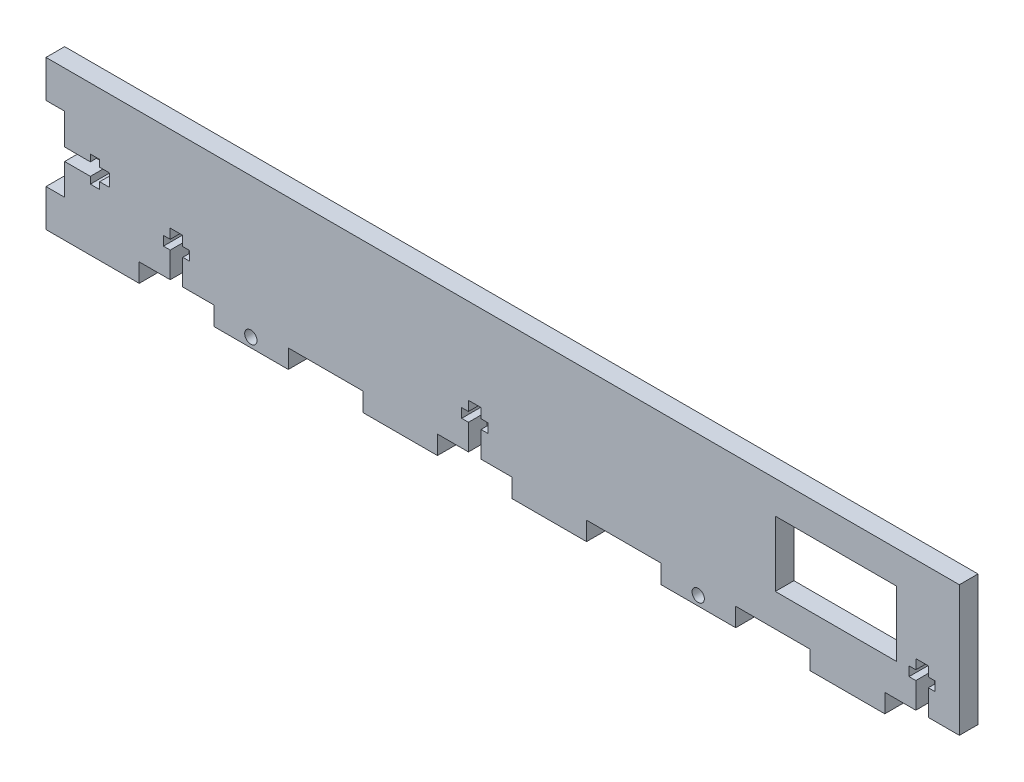
SolidWorks part; units mm, degrees
ref_plane "Front Plane" through (0, 0, 0) normal (0, 0, 1) x (1, 0, 0)
ref_plane "Top Plane" through (0, 0, 0) normal (0, 1, 0) x (1, 0, 0)
ref_plane "Right Plane" through (0, 0, 0) normal (1, 0, 0) x (0, 0, -1)
sketch "Sketch1" plane through (0, 0, 0) normal (0, 0, 1) x (1, 0, 0)
  line L0 (-262.733, -54.9538) -> (-262.733, 69.85) construction
  line L1 (42.067, 22.225) -> (-262.733, 22.225)
  line L2 (42.067, 22.225) -> (42.067, -22.225)
  line L3 (42.067, -22.225) -> (-262.733, -22.225)
  line L4 (-262.733, 22.225) -> (-262.733, -22.225)
  line L5 (63.0291, 0) -> (-62.7737, 0) construction
  line L6 (-19.6295, 10.033) -> (19.6295, 10.033) construction
  line L7 (19.6295, -10.033) -> (-19.6295, -10.033) construction
  line L8 (27.25, 6.27) -> (27.25, 8.0899) construction
  dimension "D1" = 44.45
  dimension "D2" = 14.817
extrude "Boss-Extrude1" add sketch "Sketch1" along normal blind 6.35
sketch "Sketch2" plane through (0, 0, 6.35) normal (0, 0, 1) x (1, 0, 0)
  line L0 (-41.9443, 0) -> (30.2812, 0) construction
  line L1 (-20.6375, 11.1125) -> (20.6375, 11.1125)
  line L2 (-20.6375, 11.1125) -> (-20.6375, -11.1125)
  line L3 (-20.6375, -11.1125) -> (20.6375, -11.1125)
  line L4 (20.6375, 11.1125) -> (20.6375, -11.1125)
  line L5 (-19.6295, 10.033) -> (19.6295, 10.033) construction
  line L6 (19.6295, -10.033) -> (-19.6295, -10.033) construction
  line L7 (0, 34.6052) -> (0, -28.4279) construction
  line L8 (-20.1295, -9.533) -> (-20.1295, 9.533) construction
  line L9 (20.1295, 9.533) -> (20.1295, -9.533) construction
  dimension "D1" = 22.225
  dimension "D2" = 41.275
extrude "Cut-Extrude1" cut sketch "Sketch2" against normal through all
ref_plane "Plane1" through (42.067, -22.225, 6.35) normal (1, 0, 0) x (0, 0, -1)
sketch "Sketch5" plane through (0, -22.225, 0) normal (0, -1, 0) x (1, 0, 0)
  line L0 (-262.733, 6.35) -> (42.067, 6.35) construction
  line L1 (16.667, 6.35) -> (-8.733, 6.35)
  line L2 (16.667, 6.35) -> (16.667, 0)
  line L3 (16.667, 0) -> (-8.733, 0)
  line L4 (-8.733, 6.35) -> (-8.733, 0)
  line L5 (-262.733, 0) -> (42.067, 0) construction
  dimension "D1" = 25.4
  dimension "D2" = 25.4
extrude "Boss-Extrude2" add sketch "Sketch5" along normal blind 6.35
pattern_linear "LPattern1" count 6 spacing 50.8 along (-1, 0, 0) of "Boss-Extrude2"
sketch "Sketch6" plane through (-262.733, 0, 0) normal (-1, 0, 0) x (0, 0, 1)
  line L0 (0, 22.225) -> (6.35, 22.225)
  line L1 (6.35, 22.225) -> (6.35, 9.525)
  line L2 (6.35, 22.225) -> (6.35, -28.575) construction
  line L3 (6.35, 9.525) -> (0, 9.525)
  line L4 (0, 22.225) -> (0, -28.575) construction
  line L5 (0, 9.525) -> (0, 22.225)
  dimension "D1" = 12.7
extrude "Boss-Extrude3" add sketch "Sketch6" along normal blind 6.35
pattern_linear "LPattern2" count 2 spacing 38.1 along (0, -1, 0) of "Boss-Extrude3"
sketch "Sketch7" plane through (0, 0, 6.35) normal (0, 0, 1) x (1, 0, 0)
  line L0 (-257.1687, -3.175) -> (-223.3079, -3.175) construction
  line L1 (-269.083, 9.525) -> (-262.733, 9.525) construction
  line L2 (-269.083, -15.875) -> (-262.733, -15.875) construction
  line L3 (-262.733, 9.525) -> (-262.733, -15.875) construction
  line B0 (-262.733, -1.0414) -> (-262.733, -5.3086)
  line B1 (-250.795, -5.3086) -> (-250.795, -7.62)
  line B2 (-250.795, -7.62) -> (-253.97, -7.62)
  line B3 (-253.97, -7.62) -> (-253.97, -5.3086)
  line B4 (-253.97, -5.3086) -> (-262.733, -5.3086)
  line B5 (-250.795, -5.3086) -> (-247.493, -5.3086)
  line B6 (-247.493, -5.3086) -> (-247.493, -1.0414)
  line B7 (-250.795, -1.0414) -> (-247.493, -1.0414)
  line B8 (-253.97, -1.0414) -> (-262.733, -1.0414)
  line B9 (-253.97, 1.27) -> (-253.97, -1.0414)
  line B10 (-250.795, 1.27) -> (-253.97, 1.27)
  line B11 (-250.795, -1.0414) -> (-250.795, 1.27)
sketch_block_instance "TSlot-1"
sketch_block "TSlot" parameters "D1"=3.302, "D2"=3.175
extrude "Cut-Extrude2" cut sketch "Sketch7" against normal through all
sketch "Sketch8" plane through (0, 0, 6.35) normal (0, 0, 1) x (1, 0, 0)
  line L0 (29.367, -1.7985) -> (29.367, -22.225) construction
  line L1 (16.667, -22.225) -> (42.067, -22.225) construction
  line L2 (42.067, -22.225) -> (42.067, 22.225) construction
  line L3 (16.667, -28.575) -> (16.667, -22.225) construction
  line L4 (-224.633, 2.3642) -> (-224.633, -22.225) construction
  line L5 (-237.333, -22.225) -> (-211.933, -22.225) construction
  line L6 (-237.333, -28.575) -> (-237.333, -22.225) construction
  line L7 (-211.933, -28.575) -> (-211.933, -22.225) construction
  line L8 (-123.033, 2.3642) -> (-123.033, -22.225) construction
  line L9 (-135.733, -22.225) -> (-110.333, -22.225) construction
  line L10 (-135.733, -28.575) -> (-135.733, -22.225) construction
  line L11 (-110.333, -28.575) -> (-110.333, -22.225) construction
  line B0 (-226.7666, -22.225) -> (-222.4994, -22.225)
  line B1 (-222.4994, -10.287) -> (-220.188, -10.287)
  line B2 (-220.188, -10.287) -> (-220.188, -13.462)
  line B3 (-220.188, -13.462) -> (-222.4994, -13.462)
  line B4 (-222.4994, -13.462) -> (-222.4994, -22.225)
  line B5 (-222.4994, -10.287) -> (-222.4994, -6.985)
  line B6 (-222.4994, -6.985) -> (-226.7666, -6.985)
  line B7 (-226.7666, -10.287) -> (-226.7666, -6.985)
  line B8 (-226.7666, -13.462) -> (-226.7666, -22.225)
  line B9 (-229.078, -13.462) -> (-226.7666, -13.462)
  line B10 (-229.078, -10.287) -> (-229.078, -13.462)
  line B11 (-226.7666, -10.287) -> (-229.078, -10.287)
  line B12 (-125.1666, -22.225) -> (-120.8994, -22.225)
  line B13 (-120.8994, -10.287) -> (-118.588, -10.287)
  line B14 (-118.588, -10.287) -> (-118.588, -13.462)
  line B15 (-118.588, -13.462) -> (-120.8994, -13.462)
  line B16 (-120.8994, -13.462) -> (-120.8994, -22.225)
  line B17 (-120.8994, -10.287) -> (-120.8994, -6.985)
  line B18 (-120.8994, -6.985) -> (-125.1666, -6.985)
  line B19 (-125.1666, -10.287) -> (-125.1666, -6.985)
  line B20 (-125.1666, -13.462) -> (-125.1666, -22.225)
  line B21 (-127.478, -13.462) -> (-125.1666, -13.462)
  line B22 (-127.478, -10.287) -> (-127.478, -13.462)
  line B23 (-125.1666, -10.287) -> (-127.478, -10.287)
  line B24 (27.2334, -22.225) -> (31.5006, -22.225)
  line B25 (31.5006, -10.287) -> (33.812, -10.287)
  line B26 (33.812, -10.287) -> (33.812, -13.462)
  line B27 (33.812, -13.462) -> (31.5006, -13.462)
  line B28 (31.5006, -13.462) -> (31.5006, -22.225)
  line B29 (31.5006, -10.287) -> (31.5006, -6.985)
  line B30 (31.5006, -6.985) -> (27.2334, -6.985)
  line B31 (27.2334, -10.287) -> (27.2334, -6.985)
  line B32 (27.2334, -13.462) -> (27.2334, -22.225)
  line B33 (24.922, -13.462) -> (27.2334, -13.462)
  line B34 (24.922, -10.287) -> (24.922, -13.462)
  line B35 (27.2334, -10.287) -> (24.922, -10.287)
sketch_block_instance "TSlot-2"
sketch_block_instance "TSlot-4"
sketch_block_instance "TSlot-5"
extrude "Cut-Extrude3" cut sketch "Sketch8" against normal through all
sketch "Sketch9" plane through (0, 0, 0) normal (0, 0, -1) x (-1, 0, 0)
  line L0 (44.7707, -28.575) -> (49.0379, -22.225) construction
  line L1 (59.533, -28.575) -> (34.133, -28.575) construction
  line L2 (44.7707, -28.575) -> (44.7707, -22.225) construction
  line L3 (49.0379, -28.575) -> (44.7707, -22.225) construction
  line L4 (49.0379, -22.225) -> (49.0379, -28.575) construction
  line L5 (197.1707, -28.575) -> (201.4379, -22.225) construction
  line L6 (197.1707, -28.575) -> (197.1707, -22.225) construction
  line L7 (211.933, -28.575) -> (186.533, -28.575) construction
  line L8 (201.4379, -28.575) -> (197.1707, -22.225) construction
  line L9 (201.4379, -22.225) -> (201.4379, -28.575) construction
  circle A0 centre (46.9043, -25.4) radius 2.0955
  circle A1 centre (199.3043, -25.4) radius 2.0955
  dimension "D1" = 4.191
extrude "Cut-Extrude4" cut sketch "Sketch9" against normal through all
